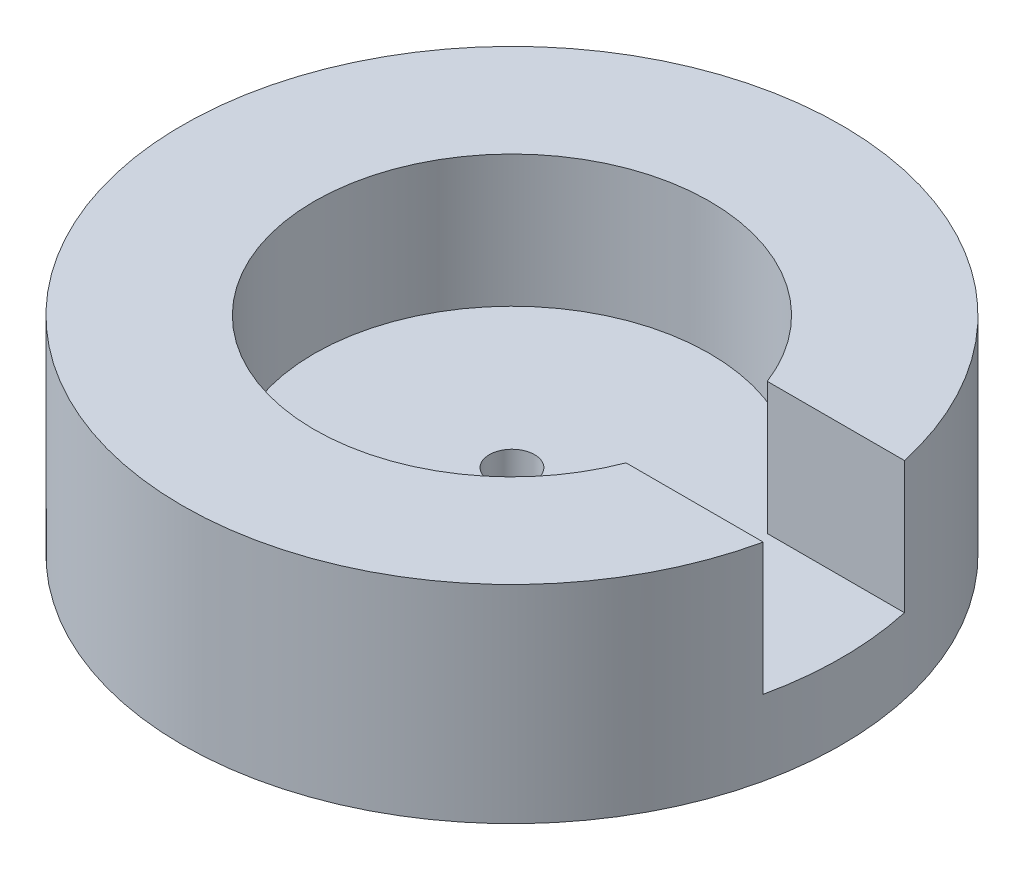
SolidWorks part; units mm, degrees
ref_plane "Front Plane" through (0, 0, 0) normal (0, 0, 1) x (1, 0, 0)
ref_plane "Top Plane" through (0, 0, 0) normal (0, 1, 0) x (1, 0, 0)
ref_plane "Right Plane" through (0, 0, 0) normal (1, 0, 0) x (0, 0, -1)
sketch "Sketch2" plane through (0, 0, 0) normal (0, 1, 0) x (1, 0, 0)
  line L0 (0, 0) -> (45.7319, 0) construction
  line L1 (0, -3.75) -> (20, -3.75)
  line L2 (0, -3.75) -> (0, 3.75)
  line L3 (0, 3.75) -> (20, 3.75)
  line L4 (20, -3.75) -> (20, 3.75)
  line L5 (0, 0) -> (20, 0) construction
  circle A0 centre (0, 0) radius 1.2
  circle A1 centre (0, 0) radius 10.5
  circle A2 centre (0, 0) radius 17.5
  dimension "D2" = 2.4
  dimension "D3" = 21
  dimension "D4" = 35
  dimension "D1" = 7.5
  dimension "D5" = 20
extrude "Boss-Extrude1" add sketch "Sketch2" against normal blind 4 contours A2
extrude "Boss-Extrude2" add sketch "Sketch2<3>" along normal blind 7 contours L3 A2 L1 A1 region at (13.4505, 0, 4.2421)
sketch "Sketch2<3>" plane through (0, 0, 0) normal (0, 1, 0) x (1, 0, 0) same geometry as "Sketch2"
extrude "Cut-Extrude1" cut sketch "Sketch2<4>" against normal blind 1.5 contours A0
sketch "Sketch2<4>" plane through (0, 0, 0) normal (0, 1, 0) x (1, 0, 0) same geometry as "Sketch2"
